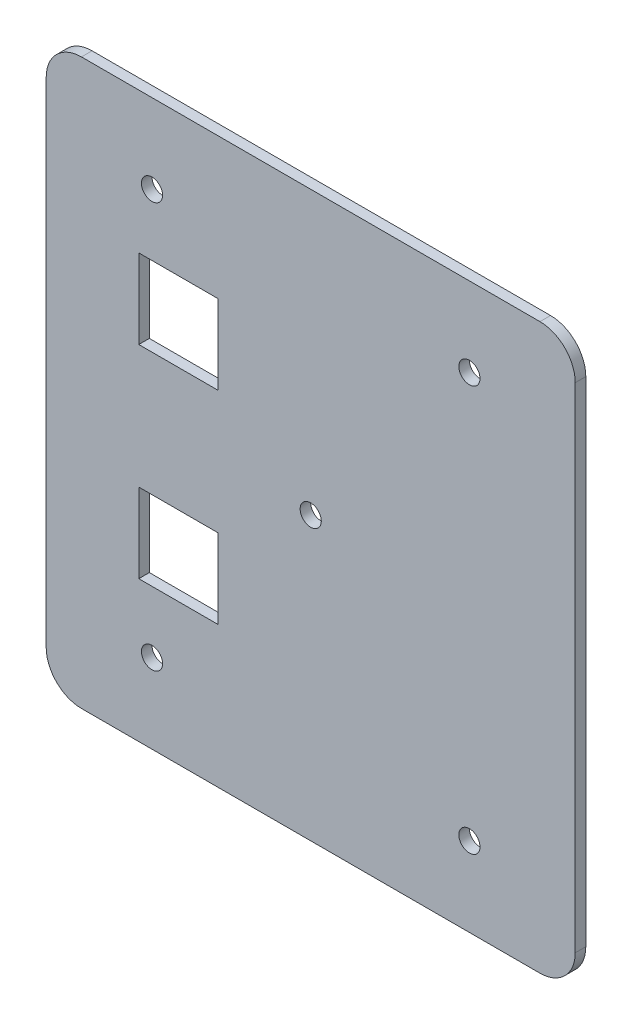
SolidWorks part; units mm, degrees
ref_plane "Front Plane" through (0, 0, 0) normal (0, 0, 1) x (1, 0, 0)
ref_plane "Top Plane" through (0, 0, 0) normal (0, 1, 0) x (1, 0, 0)
ref_plane "Right Plane" through (0, 0, 0) normal (1, 0, 0) x (0, 0, -1)
sketch "Sketch1" plane through (0, 0, 0) normal (0, 0, 1) x (1, 0, 0)
  line L0 (-22.5, -22.5) -> (22.5, -22.5) construction
  line L1 (22.5, -22.5) -> (22.5, 22.5) construction
  line L2 (22.5, 22.5) -> (-22.5, 22.5) construction
  line L3 (-22.5, 22.5) -> (-22.5, -22.5) construction
  line L4 (22.5, 92.5) -> (22.5, 137.5) construction
  line L5 (22.5, 137.5) -> (-22.5, 137.5) construction
  line L6 (-22.5, 137.5) -> (-22.5, 92.5) construction
  line L7 (-22.5, 92.5) -> (22.5, 92.5) construction
  line L8 (-22.5, -22.5) -> (22.5, -22.5)
  line L9 (22.5, -22.5) -> (22.5, 22.5)
  line L10 (22.5, 22.5) -> (-22.5, 22.5)
  line L11 (-22.5, 22.5) -> (-22.5, -22.5)
  line L12 (22.5, 92.5) -> (22.5, 137.5)
  line L13 (22.5, 137.5) -> (-22.5, 137.5)
  line L14 (-22.5, 137.5) -> (-22.5, 92.5)
  line L15 (-22.5, 92.5) -> (22.5, 92.5)
  line L16 (-22.5, 92.5) -> (22.5, 137.5)
  line L17 (-22.5, 137.5) -> (22.5, 92.5)
  line L18 (22.5, 22.5) -> (-22.5, -22.5)
  line L19 (-22.5, 22.5) -> (22.5, -22.5)
  line L20 (75, -102.5) -> (75, 57.5)
  line L21 (-55, -102.5) -> (75, -102.5)
  line L22 (-75, -82.5) -> (-75, 197.5)
  line L23 (75, -102.5) -> (75, 217.5)
  line L24 (-55, 217.5) -> (75, 217.5)
  line L25 (-75, -102.5) -> (75, 217.5) construction
  line L26 (75, -102.5) -> (-75, 217.5) construction
  line L27 (0, 0) -> (0, 57.5)
  line L28 (75, -102.5) -> (75, 217.5)
  line L29 (75, -102.5) -> (205, -102.5)
  line L30 (75, 217.5) -> (205, 217.5)
  line L31 (225, -82.5) -> (225, 197.5)
  line L32 (165, 217.5) -> (165, 172.5)
  line L33 (165, 172.5) -> (225, 172.5)
  line L34 (225, -57.5) -> (165, -57.5)
  line L35 (165, -57.5) -> (165, -102.5)
  line L36 (-15, -102.5) -> (-15, -57.5)
  line L37 (-15, -57.5) -> (-75, -57.5)
  line L38 (-75, 172.5) -> (-15, 172.5)
  line L39 (-15, 172.5) -> (-15, 217.5)
  circle A0 centre (-15, 172.5) radius 6
  circle A1 centre (165, 172.5) radius 6
  circle A2 centre (165, -57.5) radius 6
  circle A3 centre (-15, -57.5) radius 6
  circle A4 centre (75, 57.5) radius 6
  arc A5 (-75, -82.5) -> (-55, -102.5) centre (-55, -82.5) ccw
  arc A6 (205, -102.5) -> (225, -82.5) centre (205, -82.5) ccw
  arc A7 (205, 217.5) -> (225, 197.5) centre (205, 197.5) cw
  arc A8 (-75, 197.5) -> (-55, 217.5) centre (-55, 197.5) cw
  point P7 (0, 57.5)
  point P43 (225, 217.5)
  dimension "D7" = 12
  dimension "D8" = 160
  dimension "D9" = 20
  dimension "D1" = 150
  dimension "D2" = 320
  dimension "D3" = 57.5
  dimension "D4" = 150
  dimension "D5" = 60
  dimension "D6" = 45
extrude "Boss-Extrude1" add sketch "Sketch1" along normal blind 6 contours A4 L20 L29 L35 A2 L34 L31 L33 A1 L32 L30 L28 | A4 L28 L24 L39 A0 L38 L22 L37 A3 L36 L21 L20 L15 L14 L13 L12 L11 L10 L9 L8 | A0 L39 L24 L22 L38 | A1 L33 L31 L30 L32 | A2 L35 L29 L31 L34 | A3 L37 L22 L21 L36 region at (6.2964, 57.5, 0) region at (144.3054, 57.5, 0) region at (-44.4526, -79.6196, 0) region at (194.4526, -79.6196, 0) region at (-44.4526, 194.6196, 0) region at (194.4526, 194.6196, 0)
